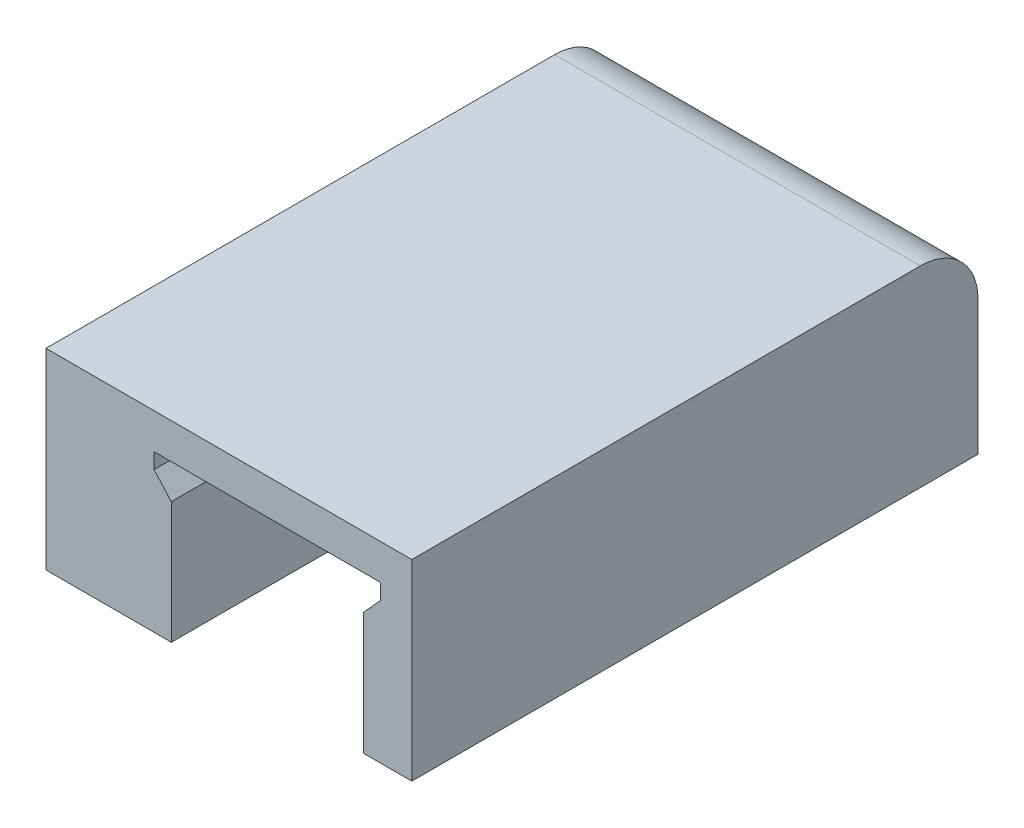
SolidWorks part; units mm, degrees
ref_plane "前视基准面" through (0, 0, 0) normal (0, 0, 1) x (1, 0, 0)
ref_plane "上视基准面" through (0, 0, 0) normal (0, 1, 0) x (1, 0, 0)
ref_plane "右视基准面" through (0, 0, 0) normal (1, 0, 0) x (0, 0, -1)
other "Configuration Table"
sketch "草图1" plane through (0, 0, 0) normal (1, 0, 0) x (0, 0, -1)
  line L5 (-14.75, 5) -> (14.75, 5)
  line L6 (-14.75, 5) -> (-14.75, -5)
  line L7 (-14.75, -5) -> (14.75, -5)
  line L8 (14.75, 5) -> (14.75, -5)
  line L9 (-14.75, 5) -> (14.75, -5) construction
  line L10 (-14.75, -5) -> (14.75, 5) construction
  point P0 (0, 0)
  dimension "D1" = 29.5
  dimension "D2" = 10
extrude "凸台-拉伸1" add sketch "草图1" along normal blind 13.06
fillet "圆角1" radius 3 1 edges at (6.53, 5, -14.75)
sketch "草图3" plane through (0, 0, 14.75) normal (0, 0, 1) x (1, 0, 0)
  line L0 (1.68, -6.8549) -> (1.68, 1.4) construction
  line L1 (1.68, 1.4) -> (0.78, 2.4) construction
  line L2 (0.78, 2.4) -> (0.78, 3) construction
  line L3 (0.78, 3) -> (12.28, 3) construction
  line L4 (12.28, 3) -> (12.28, 2.4) construction
  line L5 (12.28, 2.4) -> (11.38, 1.4) construction
  line L6 (11.38, 1.4) -> (11.38, -6.8549) construction
  line L7 (11.38, -6.8549) -> (1.68, -6.8549) construction
  line L9 (13.06, 5) -> (0, 5) construction
  line L10 (11.53, -7.0049) -> (1.53, -7.0049)
  line L11 (1.53, -7.0049) -> (1.53, 1.3424)
  line L12 (1.53, 1.3424) -> (0.63, 2.3424)
  line L13 (0.63, 2.3424) -> (0.63, 3.15)
  line L14 (0.63, 3.15) -> (12.43, 3.15)
  line L15 (12.43, 3.15) -> (12.43, 2.3424)
  line L16 (12.43, 2.3424) -> (11.53, 1.3424)
  line L17 (11.53, 1.3424) -> (11.53, -7.0049)
  point P9 (12.28, 2.7)
  point P13 (6.53, 5)
  point P14 (6.53, 3)
  dimension "D1" = 11.5
  dimension "D2" = 0.6
  dimension "D3" = 0.6
  dimension "D4" = 9.7
  dimension "D5" = 0.9
  dimension "D6" = 1
  dimension "D7" = 0.15
  dimension "D8" = 2
extrude "切除-拉伸1" cut sketch "草图3" against normal blind 25.35
sketch "草图4" plane through (13.06, 0, 0) normal (1, 0, 0) x (0, 0, -1)
  line L4 (14.75, -5) -> (14.75, 2)
  line L5 (11.75, 5) -> (-14.75, 5)
  line L6 (-14.75, 5) -> (-14.75, -5)
  line L7 (-14.75, -5) -> (14.75, -5)
  line L8 (14.75, -5) -> (14.75, 2)
  line L9 (11.75, 5) -> (-14.75, 5)
  line L10 (-14.75, 5) -> (-14.75, -5)
  line L11 (-14.75, -5) -> (14.75, -5)
  arc A1 (14.75, 2) -> (11.75, 5) centre (11.75, 2) ccw
  arc A2 (14.75, 2) -> (11.75, 5) centre (11.75, 2) ccw
  dimension "D1" = 0
extrude "凸台-拉伸2" add sketch "草图4" along normal blind 1
extrude "凸台-拉伸3" add sketch "草图4<3>" against normal blind 5 from surface starting at face at (0, 0.5243, -2.4743)
sketch "草图4<3>" plane through (13.06, 0, 0) normal (1, 0, 0) x (0, 0, -1) same geometry as "草图4"
